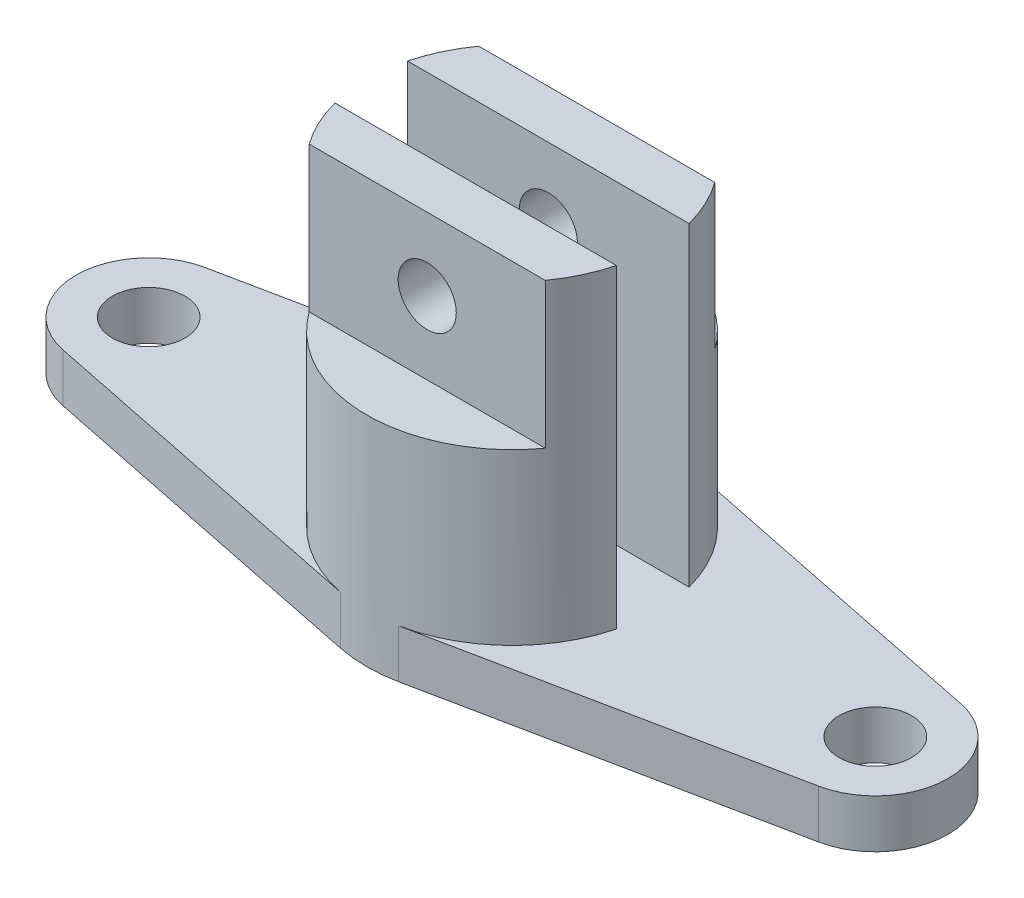
SolidWorks part; units mm, degrees
ref_plane "Front Plane" through (0, 0, 0) normal (0, 0, 1) x (1, 0, 0)
ref_plane "Top Plane" through (0, 0, 0) normal (0, 1, 0) x (1, 0, 0)
ref_plane "Right Plane" through (0, 0, 0) normal (1, 0, 0) x (0, 0, -1)
sketch "Sketch3" plane through (0, 0, 0) normal (0, 1, 0) x (1, 0, 0)
  line L0 (-1905, 0) -> (1140.1319, 0) construction
  line L7 (-152.4, 746.6045) -> (-1981.2, 373.3022)
  line L8 (-618.9214, 444.5) -> (618.9214, 444.5)
  line L9 (-618.9214, 444.5) -> (-618.9214, -444.5) construction
  line L10 (-618.9214, -444.5) -> (618.9214, -444.5)
  line L11 (618.9214, 444.5) -> (618.9214, -444.5) construction
  line L12 (-737.8033, 190.5) -> (737.8033, 190.5)
  line L14 (-737.8033, -190.5) -> (737.8033, -190.5)
  line L16 (152.4, 746.6045) -> (1981.2, 373.3022)
  line L17 (-1981.2, -373.3022) -> (-152.4, -746.6045)
  line L18 (152.4, -746.6045) -> (1981.2, -373.3022)
  arc A0 (-1981.2, 373.3022) -> (-1981.2, -373.3022) centre (-1905, 0) ccw
  arc A1 (1981.2, -373.3022) -> (1981.2, 373.3022) centre (1905, 0) ccw
  arc A2 (-737.8033, -190.5) -> (737.8033, -190.5) centre (0, 0) ccw
  circle A3 centre (-1905, 0) radius 190.5
  circle A4 centre (1905, 0) radius 190.5
  arc A5 (737.8033, 190.5) -> (-737.8033, 190.5) centre (0, 0) ccw
  point P11 (-2286, 0)
  dimension "D1" = 762
  dimension "D2" = 1524
  dimension "D3" = 381
  dimension "D5" = 2286
  dimension "D4" = 3810
  dimension "D6" = 889
  dimension "D7" = 381
  dimension "D8" = 190.5
extrude "Boss-Extrude1" add sketch "Sketch3" along normal blind 1905 contours L10 A2 L14 | L12 A5 L8 region at (0, 0, -313.8731) region at (0, 0, 313.8731)
extrude "Boss-Extrude2" add sketch "Sketch3<3>" along normal blind 1143 contours A2 L10 | L8 A5 region at (0, 0, -574.0819) region at (0, 0, 574.0819)
sketch "Sketch3<3>" plane through (0, 0, 0) normal (0, 1, 0) x (1, 0, 0) same geometry as "Sketch3"
extrude "Boss-Extrude3" add sketch "Sketch3<4>" along normal blind 254 contours A5 L12 L7 A0 L17 A2 L14 L18 A1 L16 A3 A4 region at (0, 0, 0)
sketch "Sketch3<4>" plane through (0, 0, 0) normal (0, 1, 0) x (1, 0, 0) same geometry as "Sketch3"
sketch "Sketch4" plane through (0, 0, 444.5) normal (0, 0, 1) x (1, 0, 0)
  circle A0 centre (0, 1524) radius 152.4
  dimension "D3" = 304.8
  dimension "D1" = 2286
  dimension "D2" = 1524
extrude "Cut-Extrude1" cut sketch "Sketch4" against normal blind 1264.92
